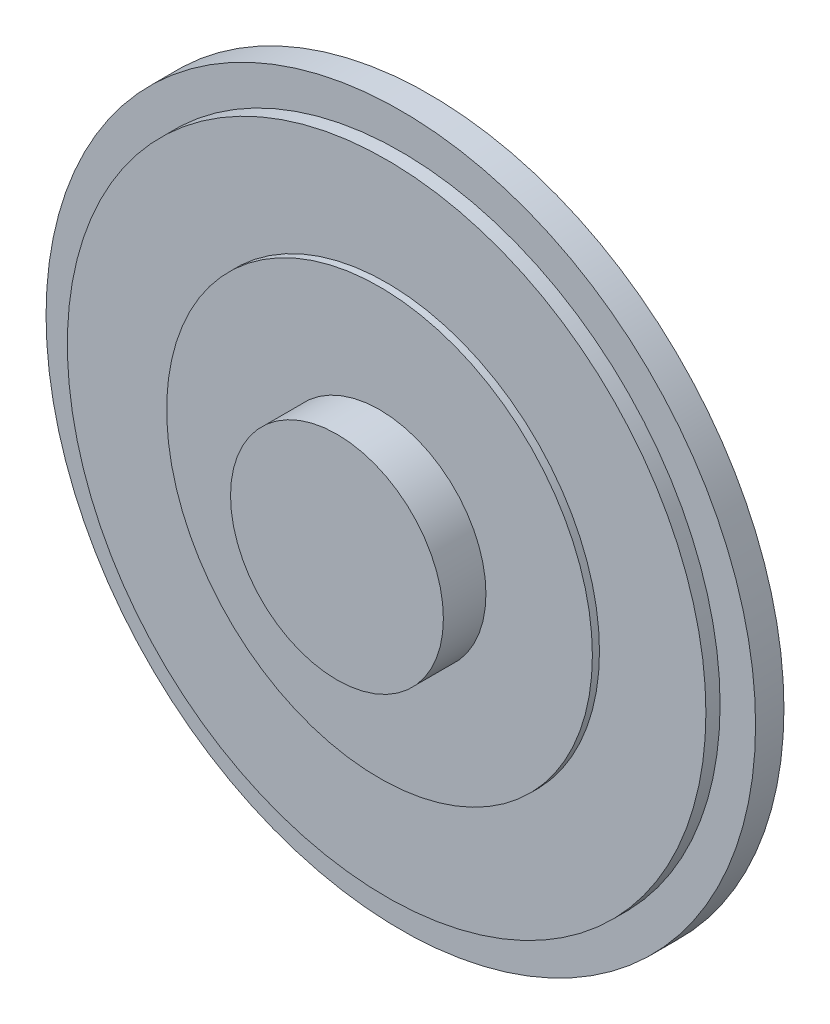
SolidWorks part; units mm, degrees
ref_plane "Front Plane" through (0, 0, 0) normal (0, 0, 1) x (1, 0, 0)
ref_plane "Top Plane" through (0, 0, 0) normal (0, 1, 0) x (1, 0, 0)
ref_plane "Right Plane" through (0, 0, 0) normal (1, 0, 0) x (0, 0, -1)
sketch "Sketch1" plane through (0, 0, 0) normal (0, 0, 1) x (1, 0, 0)
  circle A0 centre (0, 0) radius 25
  circle A1 centre (0, 0) radius 22.5
  circle A2 centre (0, 0) radius 15
  circle A3 centre (0, 0) radius 7.5
  dimension "D1" = 50
  dimension "D2" = 45
  dimension "D3" = 30
  dimension "D4" = 15
extrude "Boss-Extrude1" add sketch "Sketch1" along normal blind 2 contours A0 A1 | A1 A2 | A2 A3 | A3 region at (-24.2929, 0, 0) region at (-21.8636, 0, 0) region at (-14.5757, 0, 0) region at (0, 0, 0)
extrude "Boss-Extrude2" add sketch "Sketch1<3>" along normal blind 1 from surface contours A1 A2 | A2 A3 | A3 region at (-21.8636, 0, 0) region at (-14.5757, 0, 0) region at (0, 0, 0) starting at face at (25, 0, 2)
sketch "Sketch1<3>" plane through (0, 0, 0) normal (0, 0, 1) x (1, 0, 0) same geometry as "Sketch1"
extrude "Boss-Extrude3" add sketch "Sketch1<4>" along normal blind 0.5 from surface contours A2 A3 | A3 region at (-14.5757, 0, 0) region at (0, 0, 0) starting at face at (22.5, 0, 3)
sketch "Sketch1<4>" plane through (0, 0, 0) normal (0, 0, 1) x (1, 0, 0) same geometry as "Sketch1"
extrude "Boss-Extrude4" add sketch "Sketch1<5>" along normal blind 3 from surface contours A3 region at (0, 0, 0) starting at face at (15, 0, 3.5)
sketch "Sketch1<5>" plane through (0, 0, 0) normal (0, 0, 1) x (1, 0, 0) same geometry as "Sketch1"
